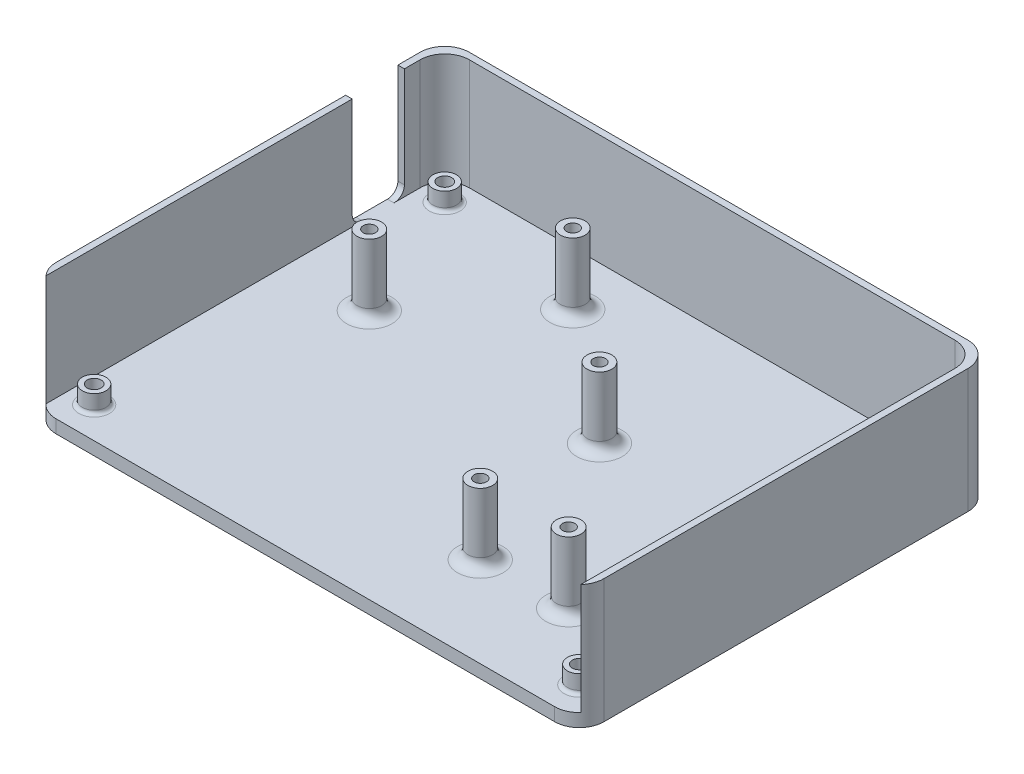
SolidWorks part; units mm, degrees
ref_plane "Front Plane" through (0, 0, 0) normal (0, 0, 1) x (1, 0, 0)
ref_plane "Top Plane" through (0, 0, 0) normal (0, 1, 0) x (1, 0, 0)
ref_plane "Right Plane" through (0, 0, 0) normal (1, 0, 0) x (0, 0, -1)
sketch "Sketch1" plane through (0, 0, 0) normal (0, 1, 0) x (1, 0, 0)
  line L0 (-66.8583, -50.2762) -> (-65.2708, -50.2762)
  line L1 (-65.2708, -50.2762) -> (64.8554, -50.2762)
  line L2 (-66.8583, -50.2762) -> (-66.8583, 44.2663)
  line L3 (-60.8583, 50.2663) -> (60.4429, 50.2663)
  line L4 (66.4429, -50.2762) -> (66.4429, 44.2663)
  line L5 (66.4429, -50.2762) -> (64.8554, -50.2762)
  line L6 (-50.3864, 41.1329) -> (-50.3864, 5.0649)
  line L7 (-50.3483, 41.1463) -> (49.9329, 41.1463)
  line L8 (-65.2708, -50.2762) -> (-65.2708, 42.6788)
  line L9 (-59.2708, 48.6788) -> (58.8554, 48.6788)
  line L10 (64.8554, -50.2762) -> (64.8554, 42.6788)
  line L11 (-50.3483, 41.1463) -> (-50.3483, -40.1162)
  line L12 (-50.3483, -40.1162) -> (49.9329, -40.1162)
  line L13 (49.9329, 41.1463) -> (49.9329, -40.1162)
  line L14 (-50.3864, 5.0649) -> (14.3836, 5.0649)
  line L15 (14.3836, 5.0649) -> (14.3836, -33.7971)
  line L16 (14.3836, -33.7971) -> (47.4036, -33.7971)
  line L17 (47.4036, -33.7971) -> (47.4036, 41.1329)
  line L18 (47.4036, 41.1329) -> (-50.3864, 41.1329)
  circle A0 centre (-59.2383, 42.6463) radius 1.7
  circle A1 centre (-59.2383, 42.6463) radius 2.875
  circle A2 centre (58.8229, 42.6463) radius 2.875
  circle A3 centre (58.8229, 42.6463) radius 1.7
  circle A4 centre (-59.2383, -42.6562) radius 2.875
  circle A5 centre (-59.2383, -42.6562) radius 1.7
  circle A6 centre (58.8229, -42.6562) radius 2.875
  circle A7 centre (58.8229, -42.6562) radius 1.7
  circle A8 centre (-21.0872, 35.6529) radius 1.5
  circle A9 centre (20.4128, -28.3471) radius 1.5
  circle A10 centre (-45.5872, 10.6529) radius 1.5
  circle A11 centre (10.4128, 10.6529) radius 1.5
  circle A12 centre (41.4128, -27.8471) radius 1.5
  arc A13 (-66.8583, 44.2663) -> (-60.8583, 50.2663) centre (-60.8583, 44.2663) cw
  arc A14 (-65.2708, 42.6788) -> (-59.2708, 48.6788) centre (-59.2708, 42.6788) cw
  circle A15 centre (-48.0512, -37.8237) radius 2
  arc A16 (58.8554, 48.6788) -> (64.8554, 42.6788) centre (58.8554, 42.6788) cw
  arc A17 (60.4429, 50.2663) -> (66.4429, 44.2663) centre (60.4429, 44.2663) cw
  circle A18 centre (-45.5872, 10.6529) radius 3
  circle A19 centre (-21.0872, 35.6529) radius 3
  circle A20 centre (10.4128, 10.6529) radius 3
  circle A21 centre (20.4128, -28.3471) radius 3
  circle A22 centre (41.4128, -27.8471) radius 3
  point P0 (0, 0)
  point P44 (-66.8583, 50.2663)
  point P53 (66.4429, 50.2663)
  dimension "D5" = 7.62
  dimension "D7" = 7.62
  dimension "D18" = 97.79
  dimension "D20" = 64.77
  dimension "D26" = 24.5
  dimension "D32" = 6
  dimension "D33" = 6
  dimension "D34" = 6
  dimension "D1" = 133.3013
  dimension "D2" = 100.5425
  dimension "D3" = 1.5875
  dimension "D4" = 1.5875
  dimension "D6" = 7.62
  dimension "D8" = 7.62
  dimension "D9" = 7.62
  dimension "D10" = 7.62
  dimension "D11" = 7.62
  dimension "D12" = 7.62
  dimension "D13" = 1.5875
  dimension "D14" = 9.12
  dimension "D15" = 16.51
  dimension "D16" = 16.51
  dimension "D17" = 81.2625
  dimension "D19" = 36.068
  dimension "D21" = 74.93
  dimension "D22" = 5.588
  dimension "D23" = 5.588
  dimension "D24" = 7.366
  dimension "D25" = 56
  dimension "D27" = 25
  dimension "D28" = 10
  dimension "D29" = 21
  dimension "D30" = 39
  dimension "D31" = 0.5
extrude "Boss-Extrude12" add sketch "Sketch1" along normal blind 3.175 contours L5 L4 A17 L3 A13 L2 L0 L1
extrude "Boss-Extrude13" add sketch "Sketch1<23>" along normal blind 30.1625 contours L10 L5 L4 L3 L2 L0 L8 L9 region at (-66.6913, 0, 3.005)
sketch "Sketch1<23>" plane through (0, 0, 0) normal (0, 1, 0) x (1, 0, 0) same geometry as "Sketch1"
extrude "Boss-Extrude15" add sketch "Sketch1<25>" along normal blind 7.525 contours A1 A0 | A2 A3 | A6 A7 | A4 A5 region at (-62.032, 0, -42.6463) region at (56.0293, 0, -42.6463) region at (-62.032, 0, 42.6562) region at (56.0293, 0, 42.6562)
sketch "Sketch1<25>" plane through (0, 0, 0) normal (0, 1, 0) x (1, 0, 0) same geometry as "Sketch1"
extrude "Cut-Extrude3" cut sketch "Sketch1<27>" along normal blind 28.575 contours A5 | A5 | A0 | A3 | A7 region at (-59.2383, 0, 42.6562)
sketch "Sketch1<27>" plane through (0, 0, 0) normal (0, 1, 0) x (1, 0, 0) same geometry as "Sketch1"
chamfer "Chamfer2" distance 1.45 angle 45 4 edges at (58.8229, 0, 44.3562) (58.8229, 0, -40.9463) (-59.2383, 0, 44.3562) (-59.2383, 0, -40.9463)
fillet "Fillet3" radius 6 2 edges at (66.4429, 15.0812, 50.2762) (-66.8583, 15.0812, 50.2762)
fillet "Fillet4" radius 0.85 1 edges at (-59.2383, 3.175, -45.5213)
fillet "Fillet5" radius 0.85 3 edges at (-59.2383, 3.175, 39.7812) (58.8229, 3.175, 39.7812) (58.8229, 3.175, -45.5213)
sketch "Sketch2" plane through (-65.2708, 0, 0) normal (1, 0, 0) x (0, 0, -1)
  line L0 (-48.3419, 3.175) -> (42.6788, 3.175) construction
  line L1 (38.8698, 3.175) -> (26.1698, 3.175)
  line L2 (38.8698, 3.175) -> (38.8698, 30.1625)
  line L3 (38.8698, 30.1625) -> (26.1698, 30.1625)
  line L4 (26.1698, 3.175) -> (26.1698, 30.1625)
  line L5 (-48.3419, 30.1625) -> (42.6788, 30.1625) construction
  line L6 (42.6788, 30.1625) -> (42.6788, 3.175) construction
  dimension "D1" = 12.7
  dimension "D2" = 3.8089
extrude "Cut-Extrude4" cut sketch "Sketch2" against normal blind 2.54
fillet "Fillet6" radius 2.54 2 edges at (-66.0646, 3.175, -38.8698) (-66.0646, 3.175, -26.1698)
extrude "Boss-Extrude16" add sketch "Sketch1<30>" along normal blind 20.32 contours A18 A10 | A19 A8 | A20 A11 | A22 A12 | A21 A9 region at (-48.5024, 0, -10.6529) region at (-24.0024, 0, -35.6529) region at (7.4976, 0, -10.6529) region at (17.4976, 0, 28.3471) region at (38.4976, 0, 27.8471)
sketch "Sketch1<30>" plane through (0, 0, 0) normal (0, 1, 0) x (1, 0, 0) same geometry as "Sketch1"
fillet "Fillet7" radius 2.54 5 edges at (41.4128, 3.175, 24.8471) (20.4128, 3.175, 25.3471) (10.4128, 3.175, -13.6529) (-21.0872, 3.175, -38.6529) (-45.5872, 3.175, -13.6529)
